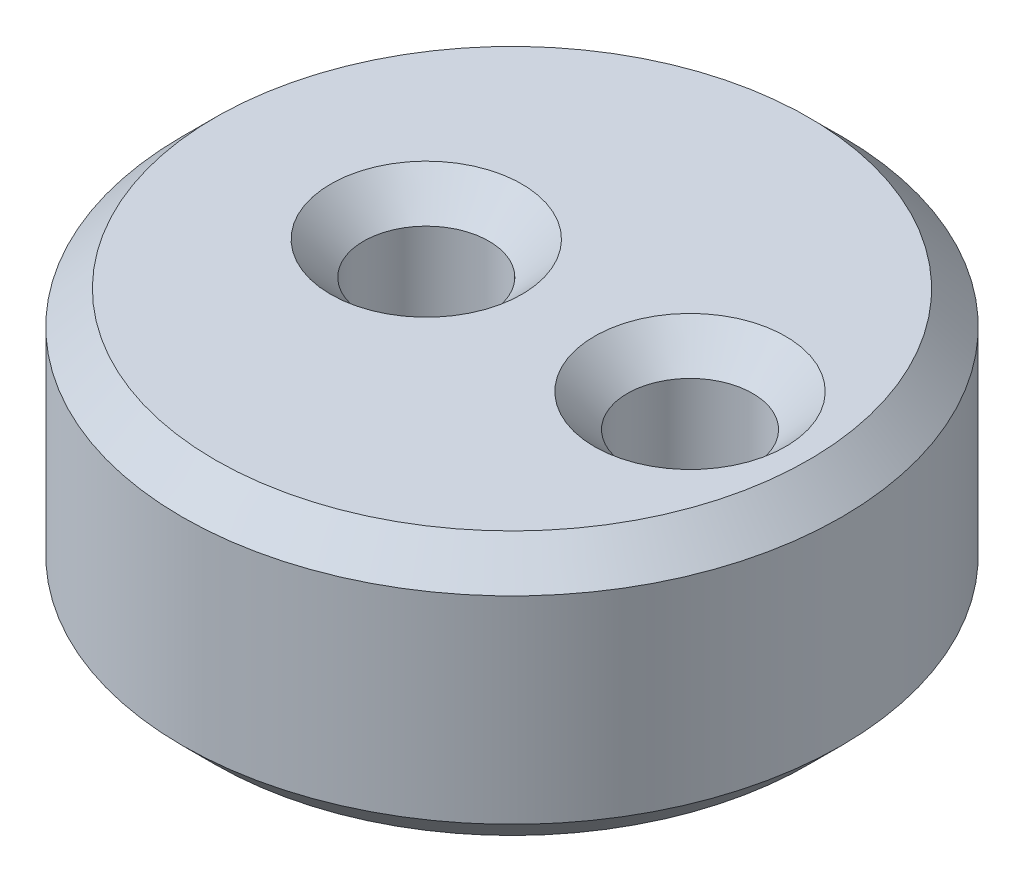
SolidWorks part; units mm, degrees
ref_plane "前视基准面" through (0, 0, 0) normal (0, 0, 1) x (1, 0, 0)
ref_plane "上视基准面" through (0, 0, 0) normal (0, 1, 0) x (1, 0, 0)
ref_plane "右视基准面" through (0, 0, 0) normal (1, 0, 0) x (0, 0, -1)
other "Configuration Table"
sketch "草图1" plane through (0, 0, 0) normal (0, 1, 0) x (1, 0, 0)
  line L0 (0.7, 6.4178) -> (0.7, -6.4114) construction
  line L1 (-5.7349, 0) -> (5.8104, 0) construction
  circle A0 centre (0, 0) radius 5
  circle A1 centre (2.7, 0) radius 0.95
  circle A2 centre (-1.3, 0) radius 0.95
  dimension "D1" = 10
  dimension "D3" = 4
  dimension "D4" = 1.9
  dimension "D2" = 0.7
extrude "凸台-拉伸1" add sketch "草图1" along normal blind 4
chamfer "倒角1" distance 0.5 angle 45 6 edges at (0, 0, 5) (0, 4, 5) (-1.3, 0, -0.95) (2.7, 0, 0.95) (-1.3, 4, -0.95) (2.7, 4, 0.95)
ref_axis "基准轴1" through (0, 3.5, 0) along (0, -1, 0)
sketch "草图2" plane through (0, 0, 0) normal (0, 1, 0) x (1, 0, 0)
  line L0 (-5.9042, 0) -> (6.2358, 0) construction
